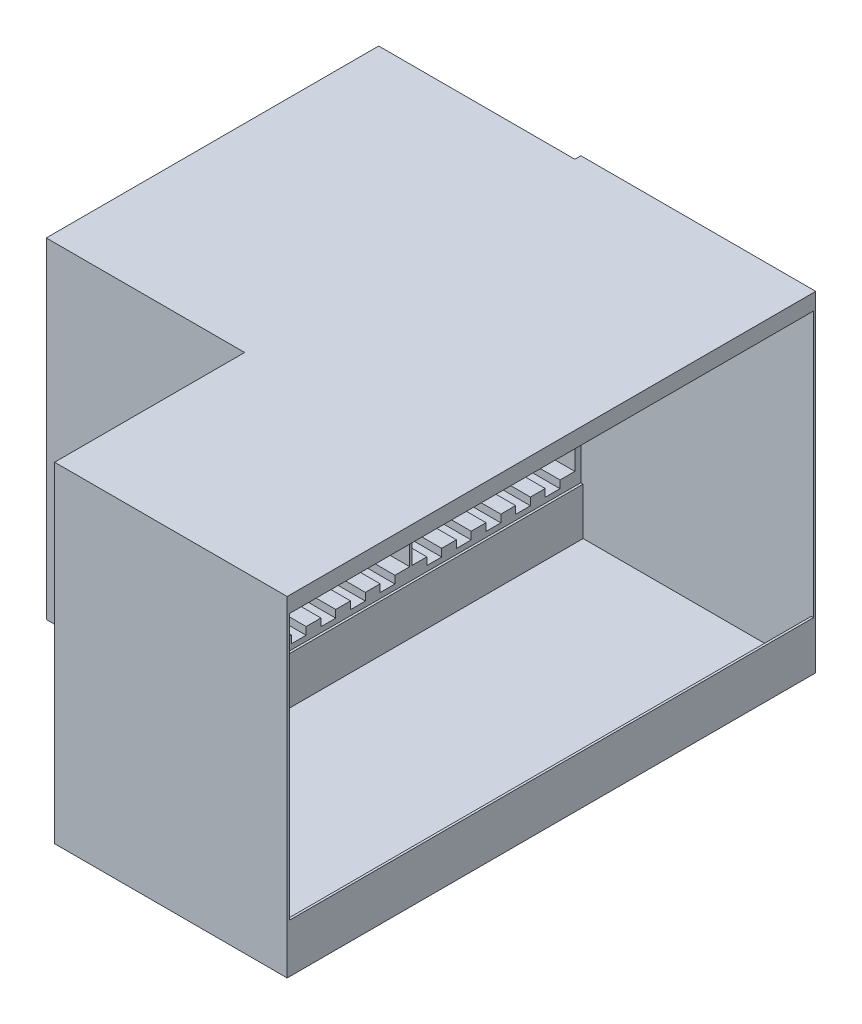
SolidWorks part; units mm, degrees
other "Исправление1"
sketch "Эскиз13" plane through (1050, -360, 1224.5) normal (0.916, -0.3443, 0.206) x (0.3981, 0.8438, -0.36)
ref_plane "Спереди" through (0, 0, 0) normal (0, 0, 1) x (1, 0, 0)
ref_plane "Сверху" through (0, 0, 0) normal (0, 1, 0) x (1, 0, 0)
ref_plane "Справа" through (0, 0, 0) normal (1, 0, 0) x (0, 0, -1)
other "Configuration Table"
sketch "Основа эскиз" plane through (0, 0, 0) normal (1, 0, 0) x (0, 0, -1)
  line L1 (-447, 436.3) -> (447, 436.3)
  line L2 (-447, 436.3) -> (-447, -436.3)
  line L3 (-447, -436.3) -> (447, -436.3)
  line L4 (447, 436.3) -> (447, -436.3)
  point P4 (0, 436.3)
  point P8 (-447, 0)
  dimension "D2" = 894
  dimension "D1" = 872.6
extrude "Основа" add sketch "Основа эскиз" along normal blind 1138.3
sketch "Вырез коретки эскиз" plane through (1138.3, 0, 0) normal (1, 0, 0) x (0, 0, -1)
  line L5 (447, 436.3) -> (-447, 436.3) construction
  line L6 (-447, 394.3) -> (441, 394.3)
  line L7 (-447, -436.3) -> (447, -436.3) construction
  line L8 (-447, 394.3) -> (-447, -305.7)
  line L9 (-447, -305.7) -> (441, -305.7)
  line L10 (441, 394.3) -> (441, -305.7)
  line L11 (-447, 436.3) -> (-447, -436.3) construction
  line L12 (447, -436.3) -> (447, 436.3) construction
  point P0 (0, 0)
  dimension "D1" = 42
  dimension "D3" = 6
  dimension "D4" = 130.6
extrude "Вырез коретки" cut sketch "Вырез коретки эскиз" against normal blind 614.3
sketch "вырез ячейки эскиз" plane through (524, 0, 0) normal (1, 0, 0) x (0, 0, -1)
  line L0 (441, 394.3) -> (-447, 394.3) construction
  line L1 (-441, 394.3) -> (-11, 394.3)
  line L2 (-441, 394.3) -> (-441, 74.3)
  line L3 (-441, 74.3) -> (-11, 74.3)
  line L4 (-11, 394.3) -> (-11, 74.3)
  line L17 (-447, 394.3) -> (-447, -305.7) construction
  dimension "D7" = 430
  dimension "D8" = 320
  dimension "D1" = 6
extrude "вырез ячейки" cut sketch "вырез ячейки эскиз" against normal blind 506
sketch "вырез двери эскиз" plane through (0, 0, 0) normal (-1, 0, 0) x (0, 0, 1)
  line L1 (11, 394.3) -> (441, 394.3)
  line L2 (11, 394.3) -> (11, 74.3)
  line L3 (11, 74.3) -> (441, 74.3)
  line L4 (441, 394.3) -> (441, 74.3)
  line L6 (441, 74.3) -> (11, 74.3) construction
  line L7 (11, 74.3) -> (11, 394.3) construction
  line L8 (441, 394.3) -> (441, 74.3) construction
  line L9 (441, 394.3) -> (441, 74.3) construction
  line L10 (11, 394.3) -> (441, 394.3) construction
extrude "вырез двери" cut sketch "вырез двери эскиз" against normal through all
sketch "Вырез основание низ эскиз" plane through (0, -305.7, 0) normal (0, 1, 0) x (1, 0, 0)
  line L0 (1138.3, -447) -> (1138.3, 441) construction
  line L1 (530, 441) -> (1132.3, 441)
  line L2 (530, 441) -> (530, -447)
  line L3 (530, -447) -> (1132.3, -447)
  line L4 (1132.3, 441) -> (1132.3, -447)
  line L5 (524, 441) -> (1138.3, 441) construction
  line L6 (524, -447) -> (1138.3, -447) construction
  dimension "D1" = 6
  dimension "D2" = 602.3
extrude "Вырез основание низ" cut sketch "Вырез основание низ эскиз" against normal blind 124.6
sketch "Вырез основания верх эскиз" plane through (0, 394.3, 0) normal (0, -1, 0) x (1, 0, 0)
  line L0 (524, 447) -> (1138.3, 447) construction
  line L1 (530, -441) -> (1132.3, -441)
  line L2 (530, -441) -> (530, 447)
  line L3 (530, 447) -> (1132.3, 447)
  line L4 (1132.3, -441) -> (1132.3, 447)
  line L5 (524, -441) -> (1138.3, -441) construction
  line L6 (1138.3, -441) -> (1138.3, 447) construction
  dimension "D1" = 6
  dimension "D2" = 602.3
extrude "Вырез основание верх" cut sketch "Вырез основания верх эскиз" against normal offset from surface (36 mm away) 6 up to face at (569.15, 436.3, 0)
sketch "вырез полозья эскиз" plane through (524, 0, 0) normal (1, 0, 0) x (0, 0, -1)
  line L0 (-441, 74.3) -> (-11, 74.3) construction
  line L1 (-401.9091, 74.3) -> (-362.8182, 74.3)
  line L2 (-401.9091, 74.3) -> (-401.9091, 54.3)
  line L3 (-401.9091, 54.3) -> (-362.8182, 54.3)
  line L4 (-362.8182, 74.3) -> (-362.8182, 54.3)
  dimension "D2" = 39.0909
  dimension "D3" = 39.0909
extrude "Вырез полозья" cut sketch "вырез полозья эскиз" against normal blind 506
pattern_linear "Линейный массив полозьев" count 5 spacing 78.1818 along (0, 0, -1) of "Вырез полозья"
pattern_linear "Линейный массив ячеек" count 2 spacing 436 along (0, 0, -1) count 2 spacing 346 along (0, -1, 0) of "Линейный массив полозьев", "вырез двери", "вырез ячейки"
sketch "Основание эскиз" plane through (0, 0, 447) normal (0, 0, 1) x (1, 0, 0)
  line L0 (1138.3, -436.3) -> (1138.3, -305.7)
  line L1 (1138.3, -305.7) -> (1132.3, -305.7)
  line L2 (1132.3, -305.7) -> (1132.3, -430.3)
  line L3 (1132.3, -430.3) -> (530, -430.3)
  line L4 (530, -430.3) -> (530, -305.7)
  line L5 (530, -305.7) -> (524, -305.7)
  line L6 (524, -305.7) -> (524, -436.3)
  line L7 (1138.3, -436.3) -> (0, -436.3) construction
  line L8 (524, -436.3) -> (1138.3, -436.3)
  line L9 (1132.3, 394.3) -> (1138.3, 394.3)
  line L10 (1138.3, 394.3) -> (1138.3, 436.3)
  line L11 (1138.3, 436.3) -> (524, 436.3)
  line L12 (1138.3, 436.3) -> (0, 436.3) construction
  line L13 (524, 436.3) -> (524, 394.3)
  line L14 (524, 394.3) -> (530, 394.3)
  line L15 (530, 394.3) -> (530, 430.3)
  line L16 (530, 430.3) -> (1132.3, 430.3)
  line L17 (1132.3, 430.3) -> (1132.3, 394.3)
extrude "Основание" add sketch "Основание эскиз" along normal blind 496
sketch "Стенка боквая эскиз" plane through (0, 0, 943) normal (0, 0, 1) x (1, 0, 0)
  line L1 (1138.3, 436.3) -> (524, 436.3)
  line L2 (1138.3, 436.3) -> (1138.3, -436.3)
  line L3 (1138.3, -436.3) -> (524, -436.3)
  line L4 (524, 436.3) -> (524, -436.3)
extrude "Стенка боковая" add sketch "Стенка боквая эскиз" along normal blind 6
sketch "Эскиз14" plane through (0, 0, -447) normal (0, 0, -1) x (-1, 0, 0)
  line L0 (-1138.3, 436.3) -> (0, 436.3) construction
  line L1 (0, -436.3) -> (-518, -436.3)
  line L2 (0, -436.3) -> (0, 436.3)
  line L3 (0, 436.3) -> (-518, 436.3)
  line L4 (-518, -436.3) -> (-518, 436.3)
  line L6 (-524, -305.7) -> (-524, 394.3) construction
  dimension "D1" = 6
extrude "Вырез-Вытянуть1" cut sketch "Эскиз14" against normal offset from surface (16 mm away) 6
sketch "Эскиз15" plane through (1138.3, 0, 0) normal (1, 0, 0) x (0, 0, -1)
  line L1 (-943, -305.7) -> (441, -305.7)
  line L2 (-943, -305.7) -> (-943, -430.3)
  line L3 (-943, -430.3) -> (441, -430.3)
  line L4 (441, -305.7) -> (441, -430.3)
extrude "Вырез-Вытянуть2" cut sketch "Эскиз15" against normal up to next
sketch "Эскиз16" plane through (1138.3, 0, 0) normal (1, 0, 0) x (0, 0, -1)
  line L0 (441, -307.08) -> (441, -430.3)
  line L2 (-943, -430.3) -> (441, -430.3)
  line L3 (-943, -430.3) -> (-943, -307.08)
  line L4 (-943, -307.08) -> (441, -307.08)
  line L7 (441, -430.3) -> (441, 394.3) construction
  dimension "D1" = 123.22
extrude "Бобышка-Вытянуть1" add sketch "Эскиз16" against normal blind 6
equation "\"Ширина груза\"= 420"
equation "\"Глубина груза\"= 490"
equation "\"Высота груза\"= 297"
equation "\"Ширина ячейки\"= \"Ширина груза\" + 10"
equation "\"Глубина ячейки\"= \"Глубина груза\" + 10"
equation "\"Высота ячейки\"= \"Высота груза\" + 10 + 13"
equation "\"Колво ячеек ширина\"= 2"
equation "\"Колво ячеек высота\"= 2"
equation "\"Толщина стенки\" = 6"
equation "\"D2@Основа эскиз\"=( \"Ширина ячейки\" + \"Толщина стенки\" + \"Крепление дверцы\" ) * \"Колво ячеек ширина\" + \"Толщина стенки\"*2"
equation "\"D1@Основа эскиз\"=( \"Высота ячейки\" + \"Толщина стенки\" + \"Высота пола\" ) * \"Колво ячеек высота\" + \"Толщина стенки\" * 6 + \"Мотор X ширина корпуса\" + \"Мотор Y ширина корпуса\"+40+20"
equation "\"Крепление дверцы\"= 5"
equation "\"D7@вырез ячейки эскиз\"= \"Ширина ячейки\""
equation "\"D1@вырез ячейки эскиз\"=\"Толщина стенки\" "
equation "\"D8@вырез ячейки эскиз\"= \"Высота ячейки\""
equation "\"D1@Основа\"=\"Глубина ячейки\" + \"Глубина каретки\" + \"Толщина стенки\" * 6 + \"Ширина рейки\""
equation "\"D1@Вырез коретки\"=\"Глубина каретки\" + \"Толщина стенки\" * 2 + \"Ширина рейки\""
equation "\"D1@Вырез основание низ эскиз\"=\"Толщина стенки\" "
equation "\"Ширина рейки\"= \"Толщина шестерни\""
equation "\"D1@вырез ячейки\"= \"Глубина ячейки\" + \"Толщина стенки\""
equation "\"D1\" = \"Толщина стенки\""
equation "\"D2@Вырез основание низ эскиз\"=\"Глубина каретки\" + \"Ширина рейки\""
equation "\"Высота рейки\"= 20"
equation "\"D1@Вырез основания верх эскиз\"=\"Толщина стенки\""
equation "\"D2@Вырез основания верх эскиз\"=\"Глубина каретки\" + \"Ширина рейки\" "
equation "\"D1@Вырез основание верх\"=\"Толщина стенки\""
equation "\"D4@Вырез коретки эскиз\"=\"Толщина стенки\"  + \"Высота рейки\" + \"Отступ рейки\" + \"Мотор X ширина корпуса\" + \"Мотор Y ширина корпуса\""
equation "\"D1@Вырез коретки эскиз\"=\"Толщина стенки\"*2+30"
equation "\"D3@Вырез коретки эскиз\" = \"Толщина стенки\""
equation "\"D1@Вырез основание низ\"=\"Мотор X ширина корпуса\" + \"Мотор Y ширина корпуса\"+\"Высота рейки\" + \"Отступ рейки\""
equation "\"Высота пола\"= 20"
equation "\"Колво полозьев\"= 5"
equation "\"D1@вырез полозья эскиз\" = \"Высота пола\""
equation "\"D2@вырез полозья эскиз\" = \"Ширина ячейки\" /  ( \"Колво полозьев\" * 2 + 1 ) "
equation "\"D3@вырез полозья эскиз\"= \"Ширина ячейки\" / ( \"Колво полозьев\" * 2 + 1 )"
equation "\"D1@Вырез полозья\" = \"Глубина ячейки\" + \"Толщина стенки\""
equation "\"D1@Линейный массив полозьев\" = \"Колво полозьев\""
equation "\"D3@Линейный массив полозьев\" = \"Ширина ячейки\" /  ( \"Колво полозьев\" * 2 + 1 )  * 2"
equation "\"D1@Линейный массив ячеек\" = \"Колво ячеек ширина\""
equation "\"D2@Линейный массив ячеек\" = \"Колво ячеек высота\""
equation "\"D3@Линейный массив ячеек\" = \"Ширина ячейки\" + \"Толщина стенки\""
equation "\"D4@Линейный массив ячеек\" = \"Высота ячейки\" + \"Высота пола\" + \"Толщина стенки\""
equation "\"Отступ рейки\"= 20"
equation "\"Глубина каретки\"= \"Глубина ячейки\" + 30 + \"Мотор Y высота корпуса\" + 20"
equation "\"D1@Стенка боковая\" = \"Толщина стенки\""
equation "\"Длинна рейки\"= ( \"Ширина ячейки\" + \"Толщина стенки\" + \"Крепление дверцы\" ) * \"Колво ячеек ширина\" + \"Ширина ячейки выгрузки\" * \"Колво выгрузки\" + \"Толщина стенки\""
equation "\"D1@Основание\" = \"Длинна рейки\" -  ( \"Ширина ячейки\" + \"Толщина стенки\" + \"Крепление дверцы\" )  * \"Колво ячеек ширина\" - \"Толщина стенки\""
equation "\"Отступ шпильки\"= 26"
equation "\"Диаметр шпильки\"= 5"
equation "\"Длинна шпильки\"= ( \"Высота ячейки\" + \"Толщина стенки\" + \"Высота пола\" ) * \"Колво ячеек высота\" + ( \"Толщина стенки\" + \"Отступ рейки\" ) * 2 "
equation "\"Ширина пластины\"= 50  "
equation "\"Высота зона выгрузки\"= \"Высота ячейки\" * 2 + \"Толщина стенки\" * 2"
equation "\"Колво выгрузки\"= 1"
equation "\"D1@Вырез-Вытянуть1\"=\"Толщина стенки\""
equation "\"Ширина ячейки выгрузки\"= \"Ширина ячейки\" + \"Толщина стенки\" + \"Отступ крепления мотора фиксации\"*2"
equation "\"Отступ крепления мотора фиксации\" = 30"
equation "\"Мотор X ширина корпуса\"= 42.3"
equation "\"Мотор X высота корпуса\"= 42.3"
equation "\"Мотор X длина корпуса\"= 40"
equation "\"Мотор X вылет вала\"= 19.8"
equation "\"Мотор Y ширина корпуса\"= 42.3"
equation "\"Мотор Y высота корпуса\"= 42.3"
equation "\"Мотор Y длина корпуса\"= 48"
equation "\"Мотор Y вылет вала\"= 30"
equation "\"Мотор Z ширина корпуса\"= 42"
equation "\"Мотор Z высота корпуса\"= 42"
equation "\"Мотор Z длина корпуса\"= 40"
equation "\"Мотор Z вылет вала\"= 23"
equation "\"Мотор диаметр вала ПРЕДВ\"= 5"
equation "\"Мотор шаг крепления ПРЕДВ\"= 31"
equation "\"Мотор диаметр отверстий ПРЕДВ\"= 3"
equation "\"Мотор глубина отверстий ПРЕДВ\"= 4.5"
equation "\"Мотор диаметр буртика ПРЕДВ\"= 22"
equation "\"Мотор высота буртика ПРЕДВ\"= 2"
equation "\"Мотор диаметр шкива ПРЕДВ\"= 16"
equation "\"Мотор длина шкива ПРЕДВ\"= 12"
equation "\"Мотор отступ шкива ПРЕДВ\"= 5"
equation "\"Мотор X шаг градусов\"= 1.8"
equation "\"Мотор Y шаг градусов\"= 1.8"
equation "\"Мотор Z шаг градусов\"= 1.8"
equation "\"Мотор Y диаметр ротора\"= 25.78"
equation "\"Толщина шестерни\"= 10"
equation "\"D1@Бобышка-Вытянуть1\"=\"Толщина стенки\""
equation "\"D1@Эскиз14\"=\"Толщина стенки\""
